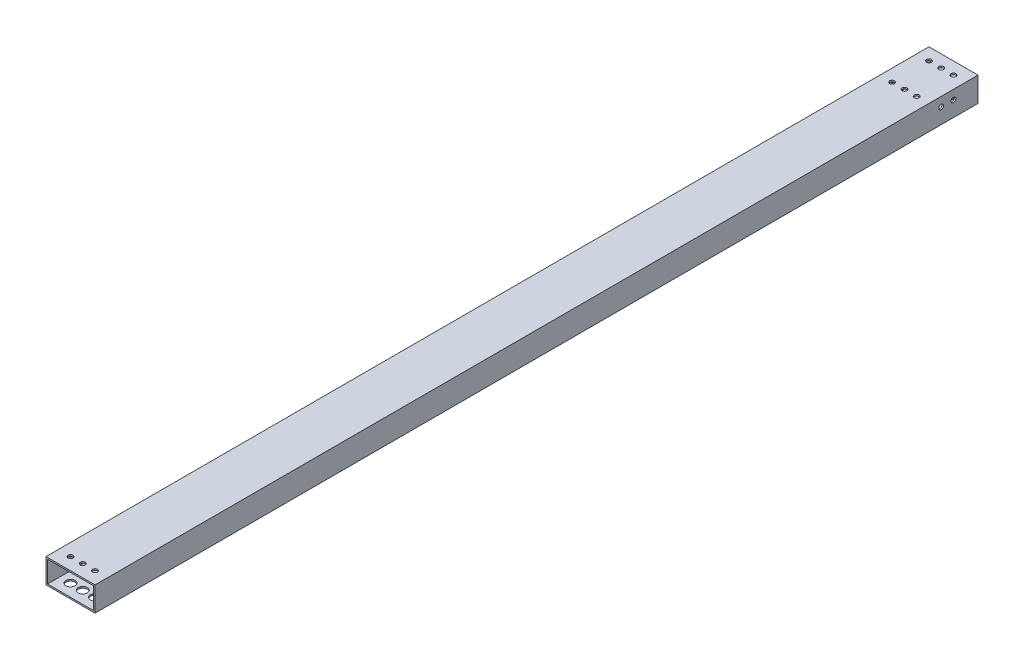
SolidWorks part; units mm, degrees
other "Markup1"
sketch "Sketch5" plane through (-25.4, -12.7, -457.2) normal (-0.35, -0.9329, -0.0852) x (-0.8023, 0.2515, 0.5413)
sketch "Sketch6" plane through (-25.4, -12.7, -457.2) normal (-0.35, -0.9329, -0.0852) x (-0.8023, 0.2515, 0.5413)
sketch "Sketch8" plane through (-25.4, -12.7, -457.2) normal (-0.35, -0.9329, -0.0852) x (-0.8023, 0.2515, 0.5413)
sketch "Sketch9" plane through (-25.4, -12.7, -457.2) normal (-0.35, -0.9329, -0.0852) x (-0.8023, 0.2515, 0.5413)
sketch "Sketch11" plane through (-25.4, -12.7, -457.2) normal (-0.35, -0.9329, -0.0852) x (-0.8023, 0.2515, 0.5413)
sketch "Sketch13" plane through (-25.4, -12.7, -457.2) normal (-0.35, -0.9329, -0.0852) x (-0.8023, 0.2515, 0.5413)
sketch "Sketch14" plane through (-25.4, -12.7, -457.2) normal (-0.35, -0.9329, -0.0852) x (-0.8023, 0.2515, 0.5413)
sketch "Sketch15" plane through (-25.4, -12.7, -457.2) normal (-0.35, -0.9329, -0.0852) x (-0.8023, 0.2515, 0.5413)
sketch "Sketch16" plane through (-25.4, -12.7, -457.2) normal (-0.35, -0.9329, -0.0852) x (-0.8023, 0.2515, 0.5413)
sketch "Sketch17" plane through (-25.4, -12.7, -457.2) normal (-0.35, -0.9329, -0.0852) x (-0.8023, 0.2515, 0.5413)
sketch "Sketch18" plane through (-25.4, -12.7, -457.2) normal (-0.35, -0.9329, -0.0852) x (-0.8023, 0.2515, 0.5413)
material "6061-T6 (SS)"
ref_plane "Front Plane" through (0, 0, 0) normal (0, 0, 1) x (1, 0, 0)
ref_plane "Top Plane" through (0, 0, 0) normal (0, 1, 0) x (1, 0, 0)
ref_plane "Right Plane" through (0, 0, 0) normal (1, 0, 0) x (0, 0, -1)
sketch "Sketch1" plane through (0, 0, 0) normal (0, 0, 1) x (1, 0, 0)
  line L0 (-23.8125, 11.1125) -> (23.8125, 11.1125)
  line L1 (-25.4, -12.7) -> (25.4, -12.7)
  line L2 (-25.4, -12.7) -> (-25.4, 12.7)
  line L3 (-25.4, 12.7) -> (25.4, 12.7)
  line L4 (25.4, -12.7) -> (25.4, 12.7)
  line L5 (-25.4, -12.7) -> (25.4, 12.7) construction
  line L6 (-25.4, 12.7) -> (25.4, -12.7) construction
  line L7 (23.8125, -11.1125) -> (23.8125, 11.1125)
  line L8 (-23.8125, -11.1125) -> (23.8125, -11.1125)
  line L9 (-23.8125, -11.1125) -> (-23.8125, 11.1125)
  point P0 (0, 0)
  dimension "D1" = 50.8
  dimension "D2" = 25.4
  dimension "D3" = 1.5875
extrude "Boss-Extrude1" add sketch "Sketch1" along normal mid plane 914.4
sketch "Sketch3" plane through (0, 12.7, 0) normal (0, 1, 0) x (1, 0, 0)
  line L2 (25.4, -457.2) -> (-25.4, -457.2) construction
  line L3 (25.4, 0) -> (-25.4, 0) construction
  line L4 (25.4, -457.2) -> (25.4, 457.2) construction
  line L5 (-25.4, -457.2) -> (-25.4, 457.2) construction
  circle A0 centre (0, -444.5) radius 2.5527
  circle A1 centre (12.7, -444.5) radius 2.5527
  circle A2 centre (-12.7, -444.5) radius 2.5527
  circle A3 centre (12.7, 444.5) radius 2.5527
  circle A4 centre (0, 444.5) radius 2.5527
  circle A5 centre (-12.7, 444.5) radius 2.5527
  dimension "D1" = 5.1054
  dimension "D2" = 12.7
  dimension "D3" = 12.7
  dimension "D4" = 12.7
extrude "Cut-Extrude2" cut sketch "Sketch3" against normal up to surface (1.5875 mm away) up to face at (0, 11.1125, 0)
sketch "Sketch4" plane through (0, -12.7, 0) normal (0, -1, 0) x (1, 0, 0)
  circle A0 centre (-12.7, 444.5) radius 2.5527 construction
  circle A1 centre (0, 444.5) radius 2.5527 construction
  circle A2 centre (12.7, 444.5) radius 2.5527 construction
  circle A3 centre (-12.7, 444.5) radius 2.5527
  circle A4 centre (0, 444.5) radius 2.5527
  circle A5 centre (12.7, 444.5) radius 2.5527
  circle A6 centre (-12.7, -444.5) radius 2.5527 construction
  circle A7 centre (0, -444.5) radius 2.5527 construction
  circle A8 centre (12.7, -444.5) radius 2.5527 construction
  circle A9 centre (-12.7, -444.5) radius 2.5527
  circle A10 centre (0, -444.5) radius 2.5527
  circle A11 centre (12.7, -444.5) radius 2.5527
  circle A12 centre (-12.7, 444.5) radius 4.7625
  circle A13 centre (0, 444.5) radius 4.7625
  circle A14 centre (12.7, 444.5) radius 4.7625
  circle A15 centre (-12.7, -444.5) radius 4.7625
  circle A16 centre (0, -444.5) radius 4.7625
  circle A17 centre (12.7, -444.5) radius 4.7625
  dimension "D1" = 9.525
  dimension "D2" = 9.525
extrude "Cut-Extrude4" cut sketch "Sketch4" against normal up to surface (1.5875 mm away) contours A12 A3 | A13 A4 | A4 | A3 | A5 | A14 A5 | A11 | A17 A11 | A16 A10 | A10 | A15 A9 | A9 region at (-12.7, -12.7, 444.5) region at (0, -12.7, 444.5) region at (12.7, -12.7, 444.5) region at (-12.7, -12.7, -444.5) region at (0, -12.7, -444.5) region at (12.7, -12.7, -444.5) region at (-17.3278, -12.7, 444.5) region at (-4.6278, -12.7, 444.5) region at (8.0722, -12.7, 444.5) region at (-17.3278, -12.7, -444.5) region at (-4.6278, -12.7, -444.5) region at (8.0722, -12.7, -444.5) up to face at (0, -11.1125, 0)
sketch "Sketch7" plane through (25.4, 0, 0) normal (1, 0, 0) x (0, 0, -1)
  line L1 (-457.2, 12.7) -> (457.2, 12.7) construction
  line L2 (0, 12.7) -> (0, -12.7) construction
  line L3 (-457.2, -12.7) -> (457.2, -12.7) construction
  line L5 (457.2, -12.7) -> (457.2, 12.7) construction
  circle A4 centre (406.4, 3.175) radius 2.4892
  circle A5 centre (419.1, 3.175) radius 2.4892
  circle A6 centre (431.8, 3.175) radius 2.4892
  circle A7 centre (444.5, 3.175) radius 2.4892
  dimension "D3" = 9.525
  dimension "D2" = 4.9784
  dimension "D1" = 12.7
  dimension "D4" = 12.7
  dimension "D5" = 12.7
  dimension "D6" = 12.7
extrude "Cut-Extrude5" cut sketch "Sketch7" against normal through all contours A5 | A6 region at (25.4, 3.175, -419.1) region at (25.4, 3.175, -431.8)
sketch "Sketch10" plane through (0, 12.7, 0) normal (0, 1, 0) x (1, 0, 0)
  line L0 (25.4, 457.2) -> (-25.4, 457.2) construction
  circle A0 centre (-12.7, 406.4) radius 2.5527
  circle A1 centre (0, 406.4) radius 2.5527
  circle A2 centre (12.7, 406.4) radius 2.5527
  dimension "D1" = 5.1054
  dimension "D2" = 12.7
  dimension "D3" = 12.7
  dimension "D4" = 50.8
extrude "Cut-Extrude6" cut sketch "Sketch10" against normal through all
